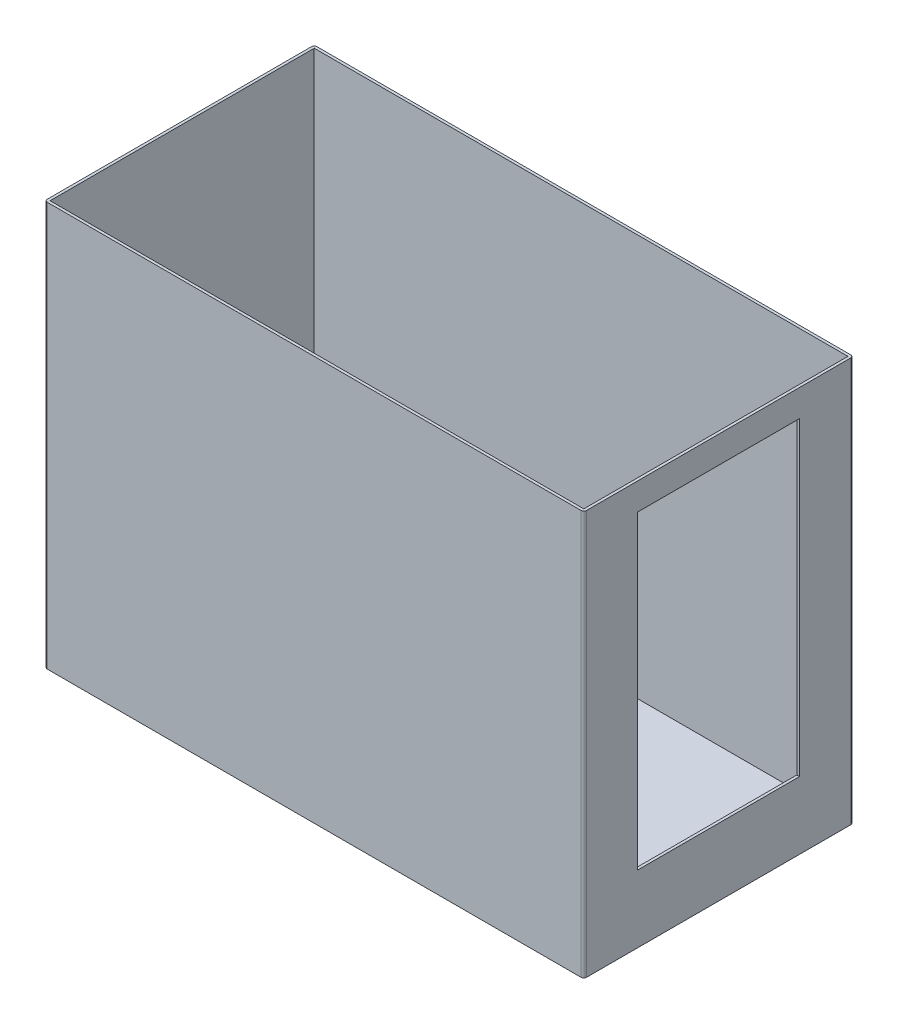
SolidWorks part; units mm, degrees
material "AISI 316 Stainless Steel Sheet (SS)"
ref_plane "Front" through (0, 0, 0) normal (0, 0, 1) x (1, 0, 0)
ref_plane "Top" through (0, 0, 0) normal (0, 1, 0) x (1, 0, 0)
ref_plane "Right" through (0, 0, 0) normal (1, 0, 0) x (0, 0, -1)
sketch "Sketch1" plane through (0, 0, 0) normal (0, 1, 0) x (1, 0, 0)
  line L1 (-200, -100) -> (200, -100)
  line L2 (-200, -100) -> (-200, 100)
  line L3 (-200, 100) -> (200, 100)
  line L4 (200, -100) -> (200, 100)
  line L5 (-200, -100) -> (200, 100) construction
  line L6 (-200, 100) -> (200, -100) construction
  point P0 (0, 0)
  dimension "D1" = 200
  dimension "D2" = 400
extrude "Boss-Extrude1" add sketch "Sketch1" along normal mid plane 300
fillet "Fillet1" radius 2 4 edges at (-200, 0, -100) (200, 0, -100) (200, 0, 100) (-200, 0, 100)
shell "Shell1" thickness 2 removed face at (0, 150, 0)
sketch "Sketch2" plane through (198, 0, 0) normal (-1, 0, 0) x (0, 0, 1)
  line L0 (0, -50) -> (0, 50) construction
  line L1 (-60, 130) -> (60, 130)
  line L2 (-60, 130) -> (-60, -100)
  line L3 (-60, -100) -> (60, -100)
  line L4 (60, 130) -> (60, -100)
  line L5 (-60, 130) -> (60, -100) construction
  line L6 (-60, -100) -> (60, 130) construction
  line L7 (98, 150) -> (-98, 150) construction
  line L8 (98, -150) -> (-98, -150) construction
  line L9 (100, -150) -> (100, 150) construction
  point P0 (0, 15)
  point P5 (0, 0)
  dimension "D1" = 20
  dimension "D2" = 50
  dimension "D3" = 120
  dimension "D4" = 40
extrude "Cut-Extrude1" cut sketch "Sketch2" against normal through all
